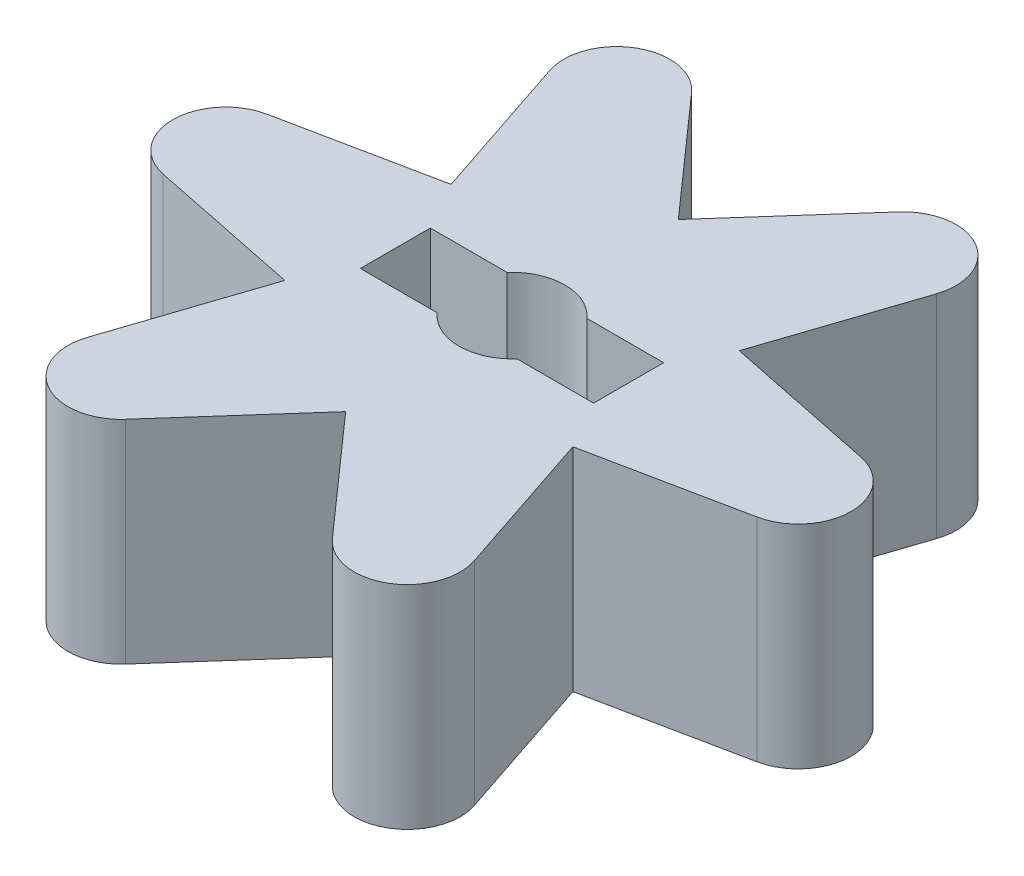
SolidWorks part; units mm, degrees
ref_plane "Front Plane" through (0, 0, 0) normal (0, 0, 1) x (1, 0, 0)
ref_plane "Top Plane" through (0, 0, 0) normal (0, 1, 0) x (1, 0, 0)
ref_plane "Right Plane" through (0, 0, 0) normal (1, 0, 0) x (0, 0, -1)
sketch "Sketch1" plane through (0, 0, 0) normal (0, 1, 0) x (1, 0, 0)
  line L0 (3.9686, -4.5) -> (14.0007, -2.4494)
  line L1 (3.9686, 4.5) -> (14.0007, 2.4494)
  line L2 (0, 0) -> (16, 0) construction
  line L3 (-1.9128, -5.6869) -> (4.8791, -13.3496)
  line L4 (5.8814, -1.1869) -> (9.1215, -10.9003)
  line L5 (-5.8814, -1.1869) -> (-9.1215, -10.9003)
  line L6 (1.9128, -5.6869) -> (-4.8791, -13.3496)
  line L7 (-3.9686, 4.5) -> (-14.0007, 2.4494)
  line L8 (-3.9686, -4.5) -> (-14.0007, -2.4494)
  line L9 (1.9128, 5.6869) -> (-4.8791, 13.3496)
  line L10 (-5.8814, 1.1869) -> (-9.1215, 10.9003)
  line L11 (5.8814, 1.1869) -> (9.1215, 10.9003)
  line L12 (-1.9128, 5.6869) -> (4.8791, 13.3496)
  circle A0 centre (0, 0) radius 6
  arc A1 (14.0007, 2.4494) -> (14.0007, -2.4494) centre (13.5, 0) cw
  arc A2 (9.1215, -10.9003) -> (4.8791, -13.3496) centre (6.75, -11.6913) cw
  arc A3 (-4.8791, -13.3496) -> (-9.1215, -10.9003) centre (-6.75, -11.6913) cw
  arc A4 (-14.0007, -2.4494) -> (-14.0007, 2.4494) centre (-13.5, 0) cw
  arc A5 (-9.1215, 10.9003) -> (-4.8791, 13.3496) centre (-6.75, 11.6913) cw
  arc A6 (4.8791, 13.3496) -> (9.1215, 10.9003) centre (6.75, 11.6913) cw
  circle A13 centre (0, 0) radius 4.75
  point P8 (-3.6416, -13.9775)
  point P10 (0, 0)
  point P33 (0, 0)
  point P36 (0, 0)
  dimension "D1" = 12
  dimension "D3" = 2.5
  dimension "D5" = 9.5
  dimension "D2" = 9
  dimension "D4" = 13.5
  dimension "D6" = 6
extrude "Boss-Extrude1" add sketch "Sketch1" along normal blind 10 contours A3 L6 L3 A0 L8 L5 | A4 L8 L5 A0 L10 L7 | A0 L5 L8 | A0 L3 L6 | A2 L4 L0 A0 L6 L3 | L2 A0 L4 L0 A1 | A0 L0 L4 | A0 L2 A1 L1 L11 | A0 L11 L1 | A6 L12 L9 A0 L1 L11 | A0 L9 L12 | A5 L10 L7 A0 L12 L9 | A0 L7 L10 | A0 region at (5.6721, 0, 3.2748) region at (5.2167, 0, 9.0356) region at (10.4334, 0, 1.5283) region at (0, 0, 6.5496) region at (-5.2167, 0, 9.0356) region at (10.4334, 0, -1.5283) region at (-5.6721, 0, 3.2748) region at (5.6721, 0, -3.2748) region at (-10.4334, 0, 0) region at (5.2167, 0, -9.0356) region at (-5.6721, 0, -3.2748) region at (0, 0, -6.5496) region at (-5.2167, 0, -9.0356)
sketch "Sketch2" plane through (0, 10, 0) normal (0, 1, 0) x (1, 0, 0)
  line L0 (-1.809, -1.5) -> (-5.35, -1.5)
  line L1 (-5.35, -1.5) -> (-5.35, 1.5)
  line L2 (-5.35, 1.5) -> (-1.809, 1.5)
  line L3 (-5.35, 0) -> (0, 0) construction
  line L4 (0, 2.35) -> (0, -2.35) construction
  line L5 (5.35, 1.5) -> (1.809, 1.5)
  line L6 (5.35, -1.5) -> (5.35, 1.5)
  line L7 (1.809, -1.5) -> (5.35, -1.5)
  line L8 (-1.8782, -1.65) -> (-5.5, -1.65)
  line L9 (-5.5, -1.65) -> (-5.5, 1.65)
  line L10 (-5.5, 1.65) -> (-1.8782, 1.65)
  line L11 (5.5, 1.65) -> (1.8782, 1.65)
  line L12 (5.5, -1.65) -> (5.5, 1.65)
  line L13 (1.8782, -1.65) -> (5.5, -1.65)
  arc A0 (-1.809, -1.5) -> (1.809, -1.5) centre (0, 0) ccw
  arc A1 (-2.35, 0) -> (-1.809, -1.5) centre (0, 0) ccw construction
  arc A2 (-1.809, 1.5) -> (-2.35, 0) centre (0, 0) ccw construction
  arc A3 (1.809, 1.5) -> (-1.809, 1.5) centre (0, 0) ccw
  arc A4 (1.809, -1.5) -> (1.809, 1.5) centre (0, 0) ccw construction
  arc A5 (1.8782, 1.65) -> (-1.8782, 1.65) centre (0, 0) ccw
  arc A6 (-1.8782, -1.65) -> (1.8782, -1.65) centre (0, 0) ccw
  point P8 (-2.35, 0)
  point P12 (0, 0)
  dimension "D1" = 4.7
  dimension "D2" = 3
  dimension "D3" = 3
  dimension "D4" = 0.15
extrude "Cut-Extrude1" cut sketch "Sketch2" against normal blind 6 contours L5 A3 L2 L1 L0 A0 L7 L6 | L8 A6 L13 L12 L11 A5 L10 L9 A3 L5 L6 L7 A0 L0 L1 L2 region at (0, 10, 0) region at (-3.6891, 10, 1.5292)
sketch "Sketch3" plane through (0, 0, 0) normal (0, -1, 0) x (1, 0, 0)
  circle A0 centre (0, 0) radius 6
  dimension "D1" = 12
extrude "Cut-Extrude2" cut sketch "Sketch3" against normal blind 2
chamfer "Chamfer1" distance 2 angle 45 1 edges at (0, 2, -6)
